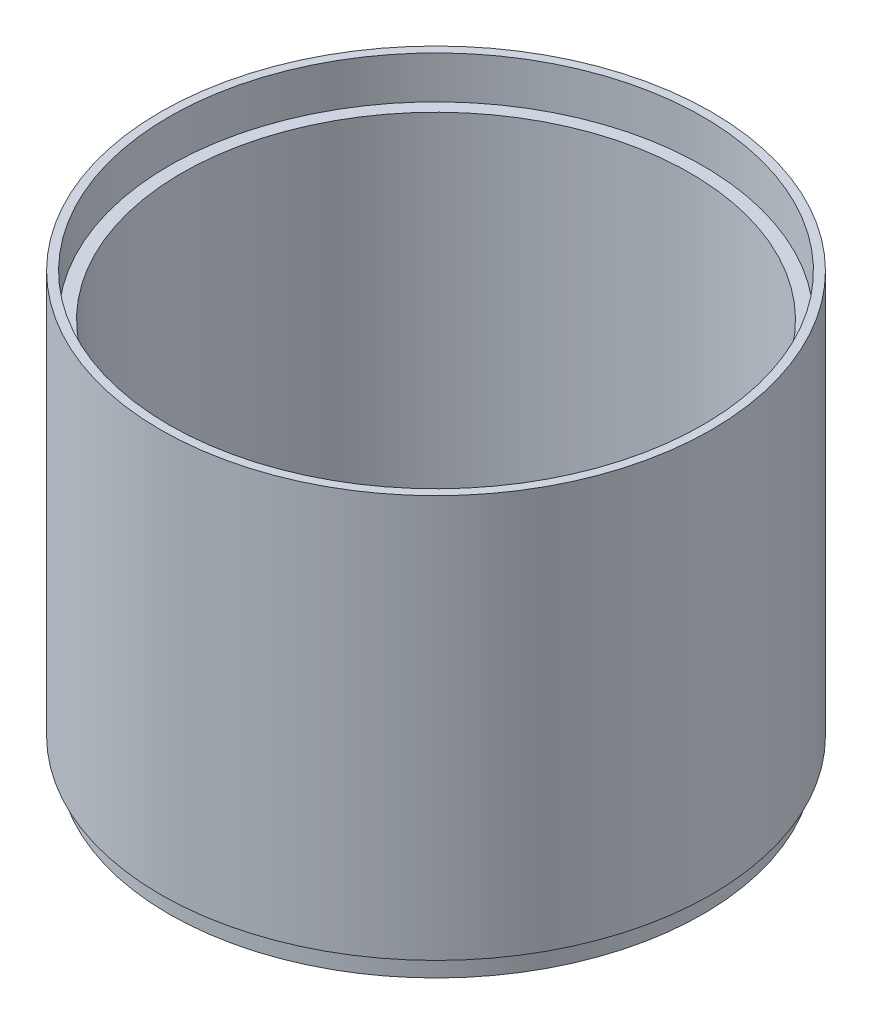
SolidWorks part; units mm, degrees
material "HYPALON"
ref_plane "Front Plane" through (0, 0, 0) normal (0, 0, 1) x (1, 0, 0)
ref_plane "Top Plane" through (0, 0, 0) normal (0, 1, 0) x (1, 0, 0)
ref_plane "Right Plane" through (0, 0, 0) normal (1, 0, 0) x (0, 0, -1)
sketch "Szkic1" plane through (0, 0, 0) normal (0, 0, 1) x (1, 0, 0)
  line L0 (-63, 0) -> (0, 0)
  line L1 (-63, 0) -> (-60, 0)
  line L2 (-63, 0) -> (-63, 5)
  line L3 (-63, 5) -> (-65, 5)
  line L4 (-65, 5) -> (-65, 28.5618)
  line L5 (-60, 0) -> (-60, 90)
  line L6 (-60, 90) -> (-63, 90)
  line L7 (-63, 90) -> (-63, 100)
  line L8 (-63, 100) -> (-65, 100)
  line L9 (-65, 100) -> (-65, 28.5618)
  line L10 (0, 35.541) -> (0, 0)
  dimension "D1" = 65
  dimension "D2" = 5
  dimension "D3" = 2
  dimension "D4" = 10
  dimension "D5" = 2
  dimension "D6" = 5
  dimension "D7" = 60
  dimension "D8" = 90
revolve "Obrót1" add sketch "Szkic1" angle 360 about L10 region at (-62.5326, 48.0978, 0)
